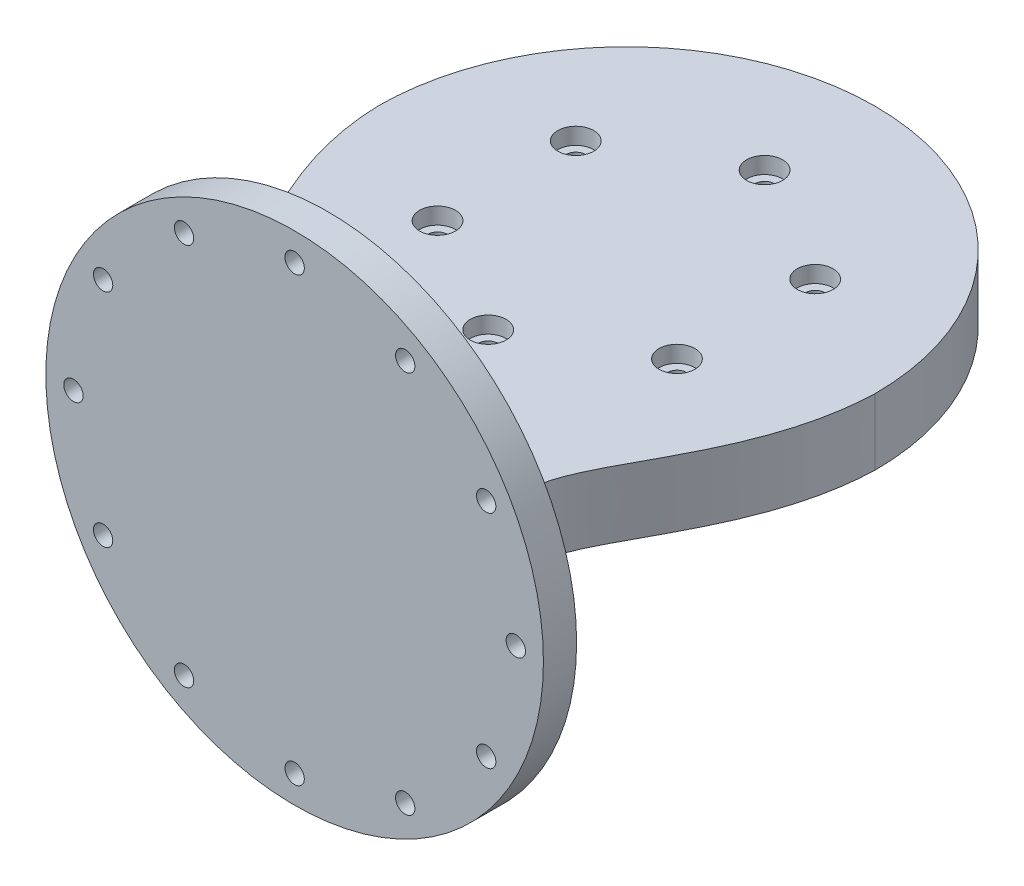
SolidWorks part; units mm, degrees
ref_plane "Front Plane" through (0, 0, 0) normal (0, 0, 1) x (1, 0, 0)
ref_plane "Top Plane" through (0, 0, 0) normal (0, 1, 0) x (1, 0, 0)
ref_plane "Right Plane" through (0, 0, 0) normal (1, 0, 0) x (0, 0, -1)
sketch "Sketch1" plane through (0, 0, 0) normal (0, 1, 0) x (1, 0, 0)
  circle A0 centre (0, 0) radius 45
  dimension "D1" = 90
extrude "Boss-Extrude1" add sketch "Sketch1" along normal blind 12
sketch "Sketch2" plane through (0, 0, 0) normal (0, -1, 0) x (1, 0, 0)
  circle A0 centre (0, 0) radius 30
  dimension "D1" = 60
extrude "Cut-Extrude1" cut sketch "Sketch2" against normal blind 6
sketch "Sketch3" plane through (0, 12, 0) normal (0, 1, 0) x (1, 0, 0)
  line L0 (0, 0) -> (0, -25) construction
  circle A0 centre (0, 0) radius 25 construction
  circle A1 centre (0, -25) radius 1.75
  circle A2 centre (-21.6506, -12.5) radius 1.75
  circle A3 centre (-21.6506, 12.5) radius 1.75
  circle A4 centre (0, 25) radius 1.75
  circle A5 centre (21.6506, 12.5) radius 1.75
  circle A6 centre (21.6506, -12.5) radius 1.75
  point P17 (0, 0)
  dimension "D1" = 50
  dimension "D2" = 3.5
  dimension "D3" = 6
extrude "Cut-Extrude2" cut sketch "Sketch3" against normal through all
sketch "Sketch4" plane through (0, 12, 0) normal (0, 1, 0) x (1, 0, 0)
  circle A0 centre (0, 25) radius 3.25
  circle A1 centre (21.6506, 12.5) radius 3.25
  circle A2 centre (21.6506, -12.5) radius 3.25
  circle A3 centre (0, -25) radius 3.25
  circle A4 centre (-21.6506, -12.5) radius 3.25
  circle A5 centre (-21.6506, 12.5) radius 3.25
  point P15 (0, 0)
  dimension "D1" = 6.5
  dimension "D2" = 6
extrude "Cut-Extrude3" cut sketch "Sketch4" against normal blind 3
sketch "Sketch5" plane through (0, 12, 0) normal (0, 1, 0) x (1, 0, 0)
  line L0 (-45, 0) -> (45, 0) construction
  line L1 (0, 0) -> (0, -45) construction
  line L2 (-45, 0) -> (-45, -60)
  line L3 (-45, -60) -> (45, -60)
  line L4 (45, -60) -> (45, 0)
  circle A0 centre (0, 0) radius 45 construction
  arc A1 (-45, 0) -> (45, 0) centre (0, 0) ccw
  circle M14 centre (0, 0) radius 45
  dimension "D1" = 60
extrude "Boss-Extrude3" add sketch "Sketch5" against normal blind 12 contours M14 region at (0, 12, 45.6258)
sketch "Sketch10" plane through (0, 0, 60) normal (0, 0, 1) x (1, 0, 0)
  line L0 (0, 12) -> (0, 0) construction
  line L1 (-45, 12) -> (45, 12) construction
  line L2 (-45, 0) -> (45, 0) construction
  circle A0 centre (0, 0) radius 45
extrude "Boss-Extrude5" add sketch "Sketch10" against normal blind 6
sketch "Sketch11" plane through (0, 0, 60) normal (0, 0, 1) x (1, 0, 0)
  line L0 (0, 0) -> (48.955, 0) construction
  circle A0 centre (0, 0) radius 40 construction
  circle A1 centre (40, 0) radius 1.75
  circle A2 centre (34.641, -20) radius 1.75
  circle A3 centre (20, -34.641) radius 1.75
  circle A4 centre (0, -40) radius 1.75
  circle A5 centre (-20, -34.641) radius 1.75
  circle A6 centre (-34.641, -20) radius 1.75
  circle A7 centre (-40, 0) radius 1.75
  circle A8 centre (-34.641, 20) radius 1.75
  circle A9 centre (-20, 34.641) radius 1.75
  circle A10 centre (0, 40) radius 1.75
  circle A11 centre (20, 34.641) radius 1.75
  circle A12 centre (34.641, 20) radius 1.75
  point P30 (0, 0)
  dimension "D1" = 80
  dimension "D2" = 3.5
  dimension "D3" = 12
sketch "Sketch14" plane through (0, 0, 0) normal (0, -1, 0) x (1, 0, 0)
  line L1 (45, 0) -> (44.1165, 28.3271) construction
  line L2 (44.1165, 28.3271) -> (18.578, 44.1158) construction
  line L3 (18.578, 44.1158) -> (33.2475, 54) construction
  line L4 (-45, 54) -> (45, 54) construction
  line L6 (45, 0) -> (45, 54)
  line L7 (45, 54) -> (33.2475, 54)
  line L8 (0, 0) -> (0, 60) construction
  line L9 (-45, 0) -> (-44.1165, 28.3271) construction
  line L10 (-44.1165, 28.3271) -> (-18.578, 44.1158) construction
  line L11 (-18.578, 44.1158) -> (-33.2475, 54) construction
  line L12 (-45, 54) -> (-33.2475, 54)
  line L13 (-45, 0) -> (-45, 54)
  circle A0 centre (0, 0) radius 45 construction
  spline S0 degree 3 poles (45, 0) (44.1165, 28.3271) (18.578, 44.1158) (33.2475, 54) knots 0 0 0 0 1 1 1 1
  spline S1 degree 3 poles (-45, 0) (-44.1165, 28.3271) (-18.578, 44.1158) (-33.2475, 54) knots 0 0 0 0 1 1 1 1
  dimension "D1" = 90
sketch "Sketch17" plane through (45, 0, 0) normal (1, 0, 0) x (0, 0, -1)
  line L0 (45, 6) -> (-60, 6) construction
  line L1 (-49, 0) -> (-54, 0)
  line L2 (-54, 0) -> (0, 0) construction
  line L3 (45, 0) -> (45, 12) construction
  line L4 (-60, 40) -> (-60, -40) construction
  line L5 (-54, 0) -> (-54, -5)
  line L8 (-54, -45) -> (-54, 0) construction
  line L9 (-54, 12) -> (-54, 17)
  line L10 (-49, 12) -> (-54, 12)
  arc A0 (-49, 0) -> (-54, -5) centre (-49, -5) ccw
  arc A1 (-49, 12) -> (-54, 17) centre (-49, 17) cw
  line M2 (0, 12) -> (-60, 12)
  line M5 (-54, 0) -> (0, 0)
  dimension "D3" = 5
  dimension "D1" = 5
  dimension "D2" = 5
extrude "Boss-Extrude7" add sketch "Sketch17" against normal through all contours L9 M2 | M5 region at (45, -1.1168, 52.8832) region at (45, 13.1168, 52.8832)
extrude "Cut-Extrude14" cut sketch "Sketch14" against normal through all both and the other way through all
extrude "Cut-Extrude15" cut sketch "Sketch11" against normal up to next
sketch "Sketch18" plane through (0, 0, 54) normal (0, 0, -1) x (-1, 0, 0)
  circle A0 centre (0, 40) radius 3.25
  circle A1 centre (20, 34.641) radius 3.25
  circle A2 centre (34.641, 20) radius 3.25
  circle A3 centre (40, 0) radius 3.25
  circle A4 centre (34.641, -20) radius 3.25
  circle A5 centre (20, -34.641) radius 3.25
  circle A6 centre (0, -40) radius 3.25
  circle A7 centre (-20, -34.641) radius 3.25
  circle A8 centre (-34.641, -20) radius 3.25
  circle A9 centre (-40, 0) radius 3.25
  circle A10 centre (-34.641, 20) radius 3.25
  circle A11 centre (-20, 34.641) radius 3.25
  point P27 (0, 0)
  dimension "D1" = 6.5
  dimension "D2" = 12
extrude "Cut-Extrude16" cut sketch "Sketch18" against normal blind 3
sketch "Sketch19" plane through (0, 0, 54) normal (0, 0, -1) x (-1, 0, 0)
  line L0 (45, 0) -> (-45, 0) construction
  line L1 (-45, 0) -> (45, 0) construction
  line L2 (-45, 0) -> (-45, 12) construction
  line L3 (0, 0) -> (0, 54.4625) construction
  circle A0 centre (-34.641, 20) radius 6
  circle A1 centre (34.641, 20) radius 6
  circle A2 centre (-34.641, -20) radius 6
  circle A3 centre (34.641, -20) radius 6
  dimension "D1" = 12
extrude "Cut-Extrude17" cut sketch "Sketch19" along normal through all
sketch "Sketch20" plane through (0, 0, 60) normal (0, 0, 1) x (1, 0, 0)
  line L0 (-45, 12) -> (-43.3705, 12) construction
  line L1 (-43.3705, 12) -> (-45, 12)
  line L2 (-45, 12) -> (-45, 0)
  line L3 (0, 0) -> (0, 45) construction
  line L4 (45, 12) -> (45, 0)
  line L5 (43.3705, 12) -> (45, 12)
  arc A0 (-45, 0) -> (-43.3705, 12) centre (0, 0) cw
  arc A1 (43.3705, 12) -> (-43.3705, 12) centre (0, 0) ccw construction
  arc A2 (45, 0) -> (43.3705, 12) centre (0, 0) ccw
extrude "Cut-Extrude18" cut sketch "Sketch20" against normal up to next
